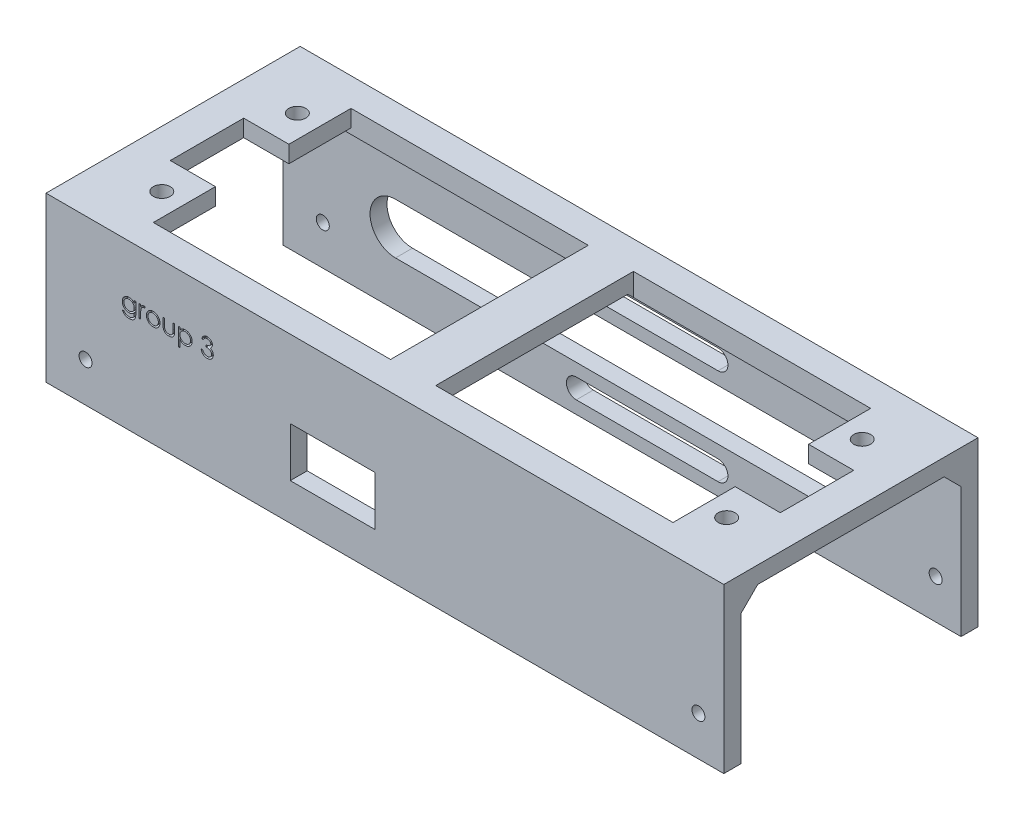
SolidWorks part; units mm, degrees
ref_plane "Front Plane" through (0, 0, 0) normal (0, 0, 1) x (1, 0, 0)
ref_plane "Top Plane" through (0, 0, 0) normal (0, 1, 0) x (1, 0, 0)
ref_plane "Right Plane" through (0, 0, 0) normal (1, 0, 0) x (0, 0, -1)
sketch "Sketch1" plane through (0, 0, 0) normal (0, 0, 1) x (1, 0, 0)
  line L9 (21.172, -17.9478) -> (91.172, -17.9478)
  line L10 (21.172, -17.9478) -> (21.172, -40.3878)
  line L11 (4, -8) -> (200.227, -8) construction
  line L12 (4, -8) -> (-67.5185, -8) construction
  line L13 (21.172, -40.3878) -> (91.172, -40.3878)
  line L14 (91.172, -17.9478) -> (91.172, -40.3878)
  line L15 (0, 0) -> (120, 0)
  line L16 (0, 0) -> (0, 29)
  line L17 (0, 29) -> (120, 29)
  line L18 (120, 0) -> (120, 29)
  circle A0 centre (4, 7) radius 1.15
  circle A1 centre (4, 7) radius 15 construction
  circle A3 centre (77.172, -29.1678) radius 3.6067
  circle A4 centre (116, 7) radius 15 construction
  circle A5 centre (116, 7) radius 1.15
  point P19 (21.172, -29.1678)
  dimension "D4" = 30
  dimension "D2" = 14
  dimension "D7" = 30
  dimension "D11" = 4
  dimension "D13" = 2.3
  dimension "D14" = 2.3
  dimension "D3" = 70
  dimension "D5" = 22.44
  dimension "D6" = 120
  dimension "D8" = 29
  dimension "D9" = 4
  dimension "D10" = 7
  dimension "D12" = 7
extrude "Boss-Extrude5" add sketch "Sketch1" along normal blind 45 contours L16 L15 L18 L17
shell "Shell9" thickness 3 removed face at (120, 14.5, 22.5) removed face at (60, 0, 22.5) removed face at (0, 14.5, 22.5)
sketch "Sketch3" plane through (0, 0, 0) normal (0, 0, -1) x (-1, 0, 0)
  line L0 (0, 0) -> (-120, 0) construction
  line L1 (-120, 0) -> (-120, 29) construction
  line L2 (0, 0) -> (0, 29) construction
  circle A0 centre (-7, 7) radius 1.15
  circle A1 centre (-115.5, 7) radius 1.15
  dimension "D1" = 2.3
  dimension "D2" = 2.3
  dimension "D3" = 7
  dimension "D4" = 4.5
  dimension "D5" = 7
  dimension "D6" = 7
extrude "Cut-Extrude2" cut sketch "Sketch3" against normal blind 79
sketch "Sketch6" plane through (0, 0, 0) normal (0, 0, -1) x (-1, 0, 0)
  line L0 (-76.9735, 21) -> (-51.8835, 21) construction
  line L1 (-76.9735, 22.75) -> (-51.8835, 22.75)
  line L2 (-76.9735, 19.25) -> (-51.8835, 19.25)
  line L7 (41.5249, -18.7743) -> (41.5249, -41.2143) construction
  line L8 (-94.8735, 12.5) -> (-19.8735, 12.5) construction
  line L9 (-94.8735, 17) -> (-19.8735, 17)
  line L10 (-94.8735, 8) -> (-19.8735, 8)
  line L11 (-19.8735, 12.5) -> (-17.326, 12.5) construction
  line L12 (-76.9735, 4) -> (-51.8835, 4) construction
  line L13 (-76.9735, 2.25) -> (-51.8835, 2.25)
  line L14 (-76.9735, 5.75) -> (-51.8835, 5.75)
  line L15 (4.7849, -29.9943) -> (74.7849, -29.9943) construction
  line L20 (4.7849, -18.7743) -> (74.7849, -18.7743)
  line L21 (4.7849, -18.7743) -> (4.7849, -41.2143)
  line L22 (4.7849, -41.2143) -> (74.7849, -41.2143)
  line L23 (74.7849, -18.7743) -> (74.7849, -41.2143)
  line L24 (-120, 0) -> (-120, 29) construction
  line L25 (63.3749, -18.7743) -> (63.3749, -41.2143) construction
  line L26 (0, 29) -> (-120, 29) construction
  arc A4 (-94.8735, 17) -> (-94.8735, 8) centre (-94.8735, 12.5) ccw
  arc A5 (-76.9735, 22.75) -> (-76.9735, 19.25) centre (-76.9735, 21) ccw
  arc A6 (-51.8835, 19.25) -> (-51.8835, 22.75) centre (-51.8835, 21) ccw
  arc A7 (-19.8735, 8) -> (-19.8735, 17) centre (-19.8735, 12.5) ccw
  arc A8 (-76.9735, 2.25) -> (-76.9735, 5.75) centre (-76.9735, 4) cw
  arc A9 (-51.8835, 5.75) -> (-51.8835, 2.25) centre (-51.8835, 4) cw
  circle A15 centre (16.1349, -29.9943) radius 1.5
  circle A16 centre (36.3249, -21.4943) radius 1.5
  circle A17 centre (36.3249, -38.4943) radius 1.5
  circle A18 centre (36.3249, -38.4943) radius 1.5
  circle A19 centre (27.0349, -29.9943) radius 2.3201
  point P11 (-64.4285, 21)
  point P19 (-57.3735, 12.5)
  point P31 (-64.4285, 4)
  dimension "D8" = 1.75
  dimension "D13" = 4.5
  dimension "D10" = 3
  dimension "D14" = 3
  dimension "D9" = 25.09
  dimension "D2" = 8.5
  dimension "D3" = 17.9
  dimension "D4" = 70
  dimension "D5" = 22.44
  dimension "D6" = 36.74
  dimension "D7" = 11.35
  dimension "D11" = 5.2
  dimension "D12" = 8.5
  dimension "D15" = 22.25
  dimension "D16" = 75
  dimension "D17" = 25.1265
  dimension "D18" = 11.41
  dimension "D19" = 16.5
extrude "Cut-Extrude8" cut sketch "Sketch6" against normal blind 23 contours L10 A7 L9 | L2 A6 L1 A5 | L13 A9 L14 A8 region at (64.4285, 21, 0) region at (57.3735, 12.5, 0)
sketch "Sketch7" plane through (0, 0, 45) normal (0, 0, 1) x (1, 0, 0)
  line L1 (43.2462, 15.2962) -> (58.2462, 15.2962)
  line L2 (43.2462, 15.2962) -> (43.2462, 6.5462)
  line L3 (43.2462, 6.5462) -> (58.2462, 6.5462)
  line L4 (58.2462, 15.2962) -> (58.2462, 6.5462)
  line L5 (0, 0) -> (120, 0) construction
  line L7 (0, 0) -> (0, 29) construction
  dimension "D1" = 43.2462
  dimension "D2" = 15
  dimension "D3" = 8.75
  dimension "D4" = 15.2962
extrude "Cut-Extrude9" cut sketch "Sketch7" against normal blind 20
sketch "Sketch13" plane through (0, 29, 0) normal (0, 1, 0) x (1, 0, 0)
  line L1 (0, 0) -> (120, 0) construction
  line L3 (64, -5) -> (114, -5)
  line L4 (6, -5) -> (56, -5)
  line L5 (6, -5) -> (6, -40)
  line L6 (6, -40) -> (56, -40)
  line L7 (56, -5) -> (56, -40)
  line L8 (0, -45) -> (0, 0) construction
  line L14 (64, -5) -> (64, -40)
  line L15 (64, -40) -> (114, -40)
  line L16 (114, -5) -> (114, -40)
  line L17 (120, -45) -> (120, 0) construction
  point P10 (64.2603, -5)
  point P12 (74, -5)
  point P16 (58, -40)
  dimension "D1" = 6
  dimension "D2" = 5
  dimension "D3" = 50
  dimension "D4" = 50
  dimension "D5" = 6
  dimension "D6" = 35
  dimension "D7" = 35
  dimension "D8" = 5
extrude "Cut-Extrude14" cut sketch "Sketch13" against normal blind 10
chamfer "Chamfer2" distance 3 angle 45 2 edges at (60, 26, 42) (60, 26, 3)
sketch "Sketch17" plane through (0, 29, 0) normal (0, 1, 0) x (1, 0, 0)
  line L1 (6, -5) -> (14, -5)
  line L2 (6, -5) -> (6, -16)
  line L3 (6, -16) -> (14, -16)
  line L4 (14, -5) -> (14, -16)
  line L5 (6, -40) -> (14, -40)
  line L6 (6, -40) -> (6, -29)
  line L7 (6, -29) -> (14, -29)
  line L8 (14, -40) -> (14, -29)
  line L9 (114, -5) -> (106, -5)
  line L10 (114, -5) -> (114, -16)
  line L11 (114, -16) -> (106, -16)
  line L12 (106, -5) -> (106, -16)
  line L13 (114, -40) -> (106, -40)
  line L14 (114, -40) -> (114, -29)
  line L15 (114, -29) -> (106, -29)
  line L16 (106, -40) -> (106, -29)
  circle A0 centre (10, -10.5) radius 1.5
  circle A1 centre (10, -34.5) radius 1.5
  circle A2 centre (110, -10.5) radius 1.5
  circle A3 centre (110, -34.5) radius 1.5
  point P8 (14, -10.5)
  point P10 (14, -34.5)
  point P11 (10, -5)
  point P18 (10, -29)
  point P32 (0, 0)
  point P33 (106, -34.5)
  point P34 (110, -29)
  point P35 (0, 0)
  point P36 (110, -16)
  point P37 (106, -10.5)
  dimension "D3" = 3
  dimension "D6" = 3
  dimension "D11" = 3
  dimension "D12" = 3
  dimension "D1" = 11
  dimension "D2" = 8
  dimension "D4" = 11
  dimension "D5" = 8
  dimension "D7" = 11
  dimension "D8" = 8
  dimension "D9" = 11
  dimension "D10" = 8
extrude "Boss-Extrude6" add sketch "Sketch17" against normal blind 3
sketch "Sketch20" plane through (0, 0, 45) normal (0, 0, 1) x (1, 0, 0)
  line L0 (13.2558, 18.0126) -> (38.9246, 18.0126) construction
  text T0 "group 3"
extrude "Cut-Extrude15" cut sketch "Sketch20" against normal blind 1.5
equation "\"slot­_width\"=25.09"
equation "\"D9@Sketch6\"=\"slot­_width\""
